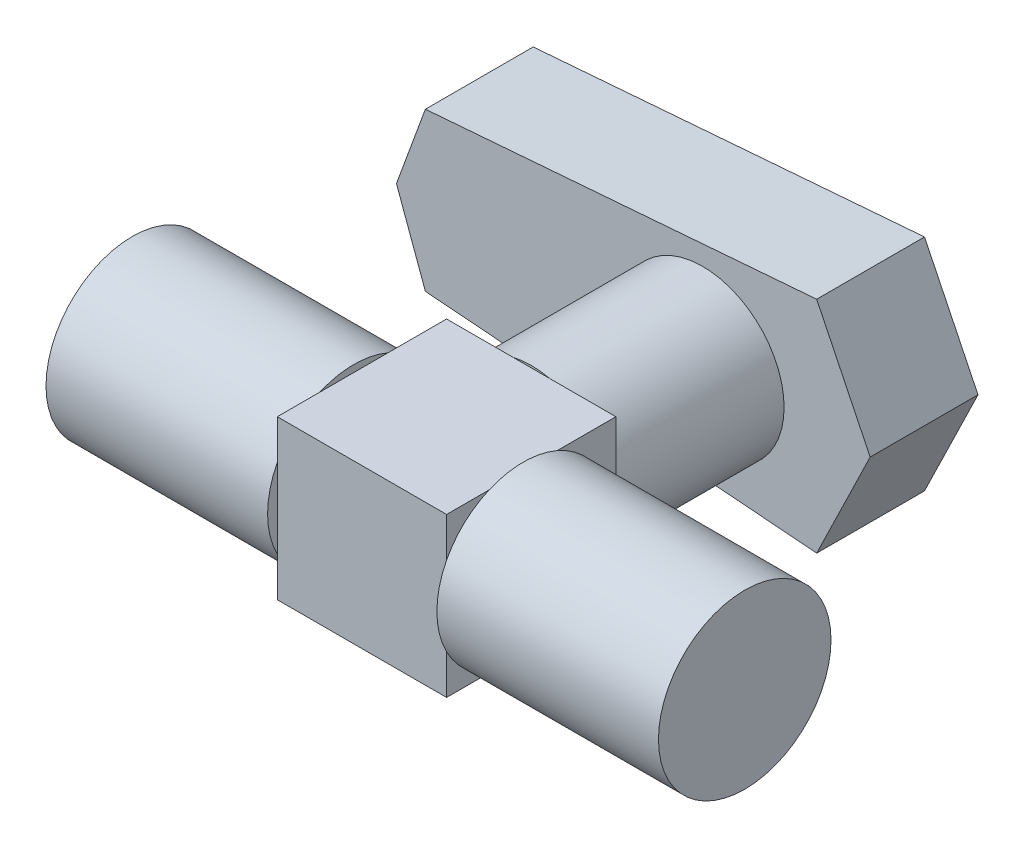
SolidWorks part; units mm, degrees
material "Brass"
ref_plane "Front Plane" through (0, 0, 0) normal (0, 0, 1) x (1, 0, 0)
ref_plane "Top Plane" through (0, 0, 0) normal (0, 1, 0) x (1, 0, 0)
ref_plane "Right Plane" through (0, 0, 0) normal (1, 0, 0) x (0, 0, -1)
sketch "Sketch2" plane through (0, 0, 0) normal (0, 1, 0) x (1, 0, 0)
  line L0 (-7.85, 7.85) -> (7.85, -7.85) construction
  line L1 (-7.85, 7.85) -> (7.85, 7.85)
  line L2 (-7.85, 7.85) -> (-7.85, -7.85)
  line L3 (-7.85, -7.85) -> (7.85, -7.85)
  line L4 (7.85, 7.85) -> (7.85, -7.85)
  line L5 (7.85, 7.85) -> (-7.85, -7.85) construction
  dimension "D1" = 15.7
  dimension "D2" = 15.7
extrude "Boss-Extrude2" add sketch "Sketch2" along normal blind 7.35 and the other way blind 7.35
sketch "Sketch3" plane through (7.85, 0, 0) normal (1, 0, 0) x (0, 0, -1)
  line L0 (7.85, -7.35) -> (7.85, 7.35) construction
  circle A0 centre (-0.75, 0) radius 8
  dimension "D2" = 16
  dimension "D1" = 8.6
extrude "Boss-Extrude3" add sketch "Sketch3" along normal blind 20.55
sketch "Sketch4" plane through (0, 0, -7.85) normal (0, 0, -1) x (-1, 0, 0)
  circle A0 centre (0, 0) radius 7.55
  dimension "D1" = 15.1
extrude "Boss-Extrude4" add sketch "Sketch4" along normal blind 25.9
sketch "Sketch5" plane through (0, 0, -33.75) normal (0, 0, -1) x (-1, 0, 0)
  line L0 (-15.5322, 0) -> (-10.5721, -10.1985)
  line L1 (-10.5721, -10.1985) -> (25.7175, -7.3136)
  line L2 (25.7175, -7.3136) -> (28.4, 0)
  line L3 (28.4, 0) -> (-15.5322, 0) construction
  line L4 (-15.5322, 0) -> (-10.5721, 10.1985)
  line L5 (-10.5721, 10.1985) -> (25.7175, 7.3136)
  line L6 (25.7175, 7.3136) -> (28.4, 0)
  point P6 (0, 0)
  dimension "D1" = 28.4
extrude "Boss-Extrude5" add sketch "Sketch5" against normal blind 10
sketch "Sketch6" plane through (0, 0, 7.85) normal (0, 0, 1) x (1, 0, 0)
  circle A0 centre (0, 0) radius 8
  dimension "D1" = 16
mirror "Mirror1" about plane through (0, 0, 0) normal (1, 0, 0) of "Boss-Extrude3"
